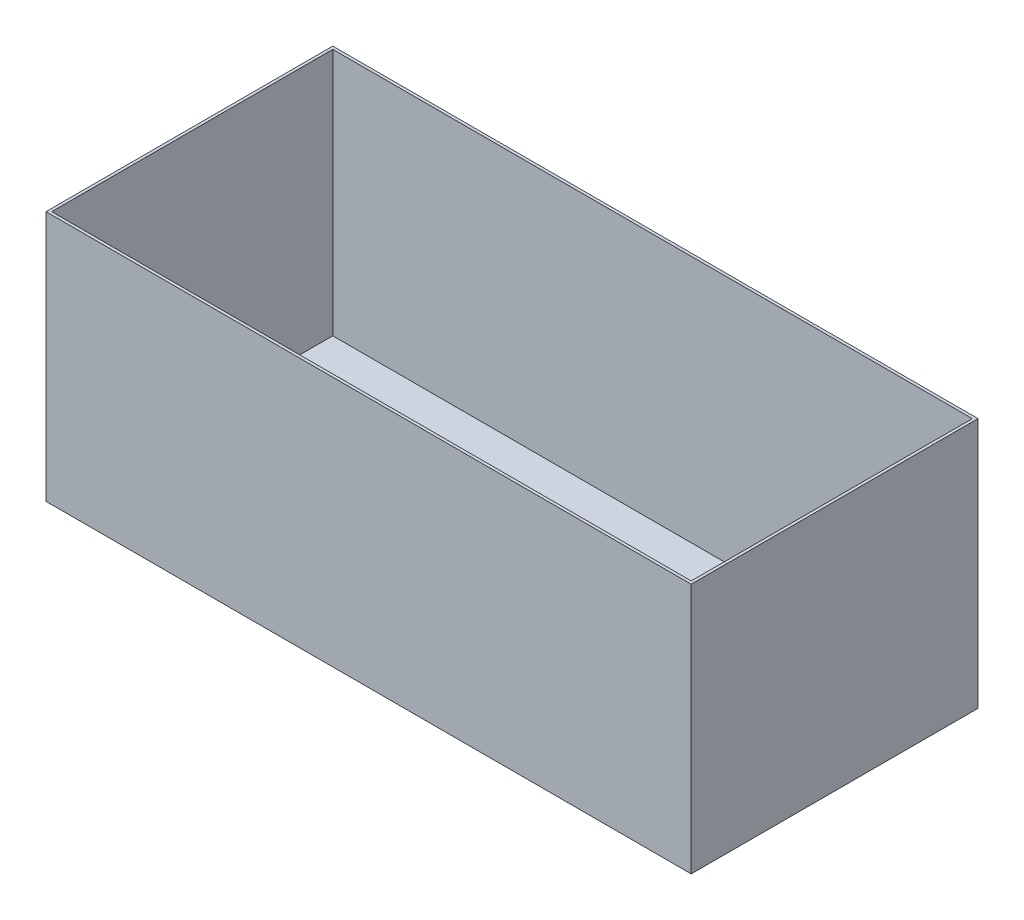
SolidWorks part; units mm, degrees
ref_plane "Front Plane" through (0, 0, 0) normal (0, 0, 1) x (1, 0, 0)
ref_plane "Top Plane" through (0, 0, 0) normal (0, 1, 0) x (1, 0, 0)
ref_plane "Right Plane" through (0, 0, 0) normal (1, 0, 0) x (0, 0, -1)
sketch "Sketch1" plane through (0, 0, 0) normal (0, 1, 0) x (1, 0, 0)
  line L1 (0, -8.4924) -> (228.6, -8.4924)
  line L2 (0, -8.4924) -> (0, 93.1076)
  line L3 (0, 93.1076) -> (228.6, 93.1076)
  line L4 (228.6, -8.4924) -> (228.6, 93.1076)
  dimension "D1" = 228.6
  dimension "D2" = 101.6
extrude "Boss-Extrude1" add sketch "Sketch1" along normal blind 88.9
shell "Shell1" thickness 1 removed face at (114.3, 88.9, -42.3076)
